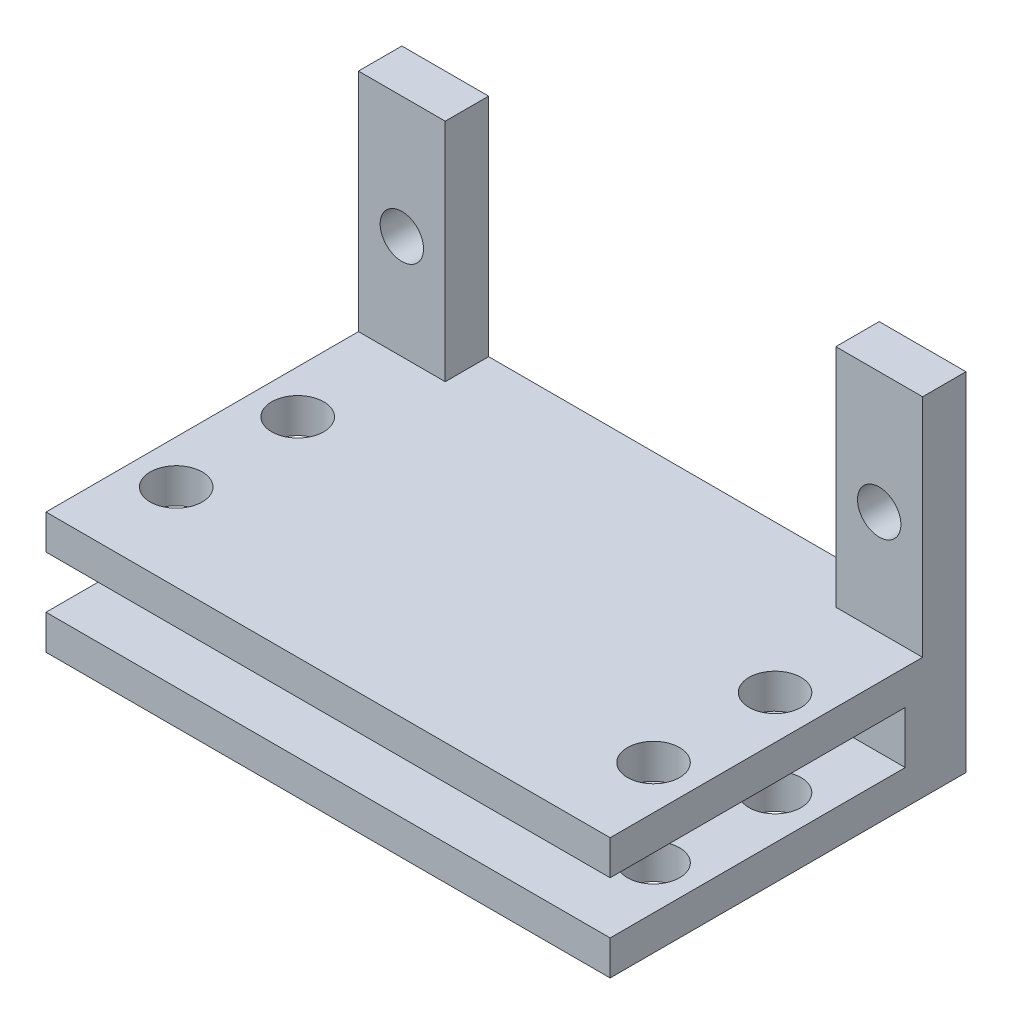
SolidWorks part; units mm, degrees
ref_plane "Front Plane" through (0, 0, 0) normal (0, 0, 1) x (1, 0, 0)
ref_plane "Top Plane" through (0, 0, 0) normal (0, 1, 0) x (1, 0, 0)
ref_plane "Right Plane" through (0, 0, 0) normal (1, 0, 0) x (0, 0, -1)
sketch "Sketch1" plane through (0, 0, 0) normal (0, 0, 1) x (1, 0, 0)
  line L0 (-16.25, 0) -> (-11.25, 0)
  line L1 (-16.25, 0) -> (-16.25, 13)
  line L2 (-16.25, 13) -> (-11.25, 13)
  line L3 (-11.25, 0) -> (-11.25, 13)
  line L8 (0, 12.0231) -> (0, -13.0504) construction
  line L9 (-16.25, 0) -> (16.25, 0)
  line L10 (-16.25, 0) -> (-16.25, -7)
  line L11 (-16.25, -7) -> (16.25, -7)
  line L13 (-16.25, -2) -> (16.25, -2)
  line L14 (-16.25, -2) -> (-16.25, -5)
  line L15 (-16.25, -5) -> (16.25, -5)
  line L17 (16.25, -2) -> (16.25, -5)
  line L18 (16.25, 0) -> (16.25, -7)
  line L19 (11.25, 0) -> (11.25, 13)
  line L20 (16.25, 13) -> (11.25, 13)
  line L21 (16.25, 0) -> (16.25, 13)
  line L22 (16.25, 0) -> (11.25, 0)
  circle A0 centre (-13.75, 6) radius 1.25
  circle A1 centre (13.75, 6) radius 1.25
  point P10 (13.75, 6)
  point P17 (0, -7)
  point P18 (0, 0)
  dimension "D7" = 6
  dimension "D8" = 2.5
  dimension "D1" = 7
  dimension "D2" = 2
  dimension "D3" = 5
  dimension "D4" = 13
  dimension "D5" = 2
  dimension "D6" = 11.25
  dimension "D9" = 2.5
extrude "Boss-Extrude1" add sketch "Sketch1" along normal blind 2.5 contours L0 L3 L2 L1 A0 | L9 L21 L20 L19 A1 region at (-16.1107, 6.5, 0) region at (11.3893, 6.5, 0)
extrude "Boss-Extrude2" add sketch "Sketch1<5>" along normal blind 20.5 contours L8 L9 L0 L10 L13 | L9 L8 L13 L18 | L8 L15 L10 L11 | L15 L8 L11 L18 region at (-8.125, -1, 0) region at (8.125, -1, 0) region at (-8.125, -6, 0) region at (8.125, -6, 0)
sketch "Sketch1<5>" plane through (0, 0, 0) normal (0, 0, 1) x (1, 0, 0) same geometry as "Sketch1"
extrude "Boss-Extrude3" add sketch "Sketch1<6>" along normal blind 3.5 contours L8 L13 L10 L15 | L13 L8 L15 L17 region at (-8.125, -3.5, 0) region at (8.125, -3.5, 0)
sketch "Sketch1<6>" plane through (0, 0, 0) normal (0, 0, 1) x (1, 0, 0) same geometry as "Sketch1"
sketch "Sketch2" plane through (0, 0, 0) normal (0, 1, 0) x (1, 0, 0)
  line L0 (0, -27.4164) -> (0, 3.5034) construction
  line L2 (16.25, -20.5) -> (16.25, -2.5) construction
  line L3 (-16.25, -20.5) -> (16.25, -20.5) construction
  circle A0 centre (13.75, -8.5) radius 1.5
  circle A1 centre (13.75, -15.5) radius 1.5
  circle A2 centre (-13.75, -15.5) radius 1.5
  circle A3 centre (-13.75, -8.5) radius 1.5
  dimension "D1" = 3
  dimension "D2" = 3
  dimension "D3" = 7
  dimension "D4" = 5
  dimension "D5" = 2.5
extrude "Cut-Extrude2" cut sketch "Sketch2" against normal through all both and the other way through all
